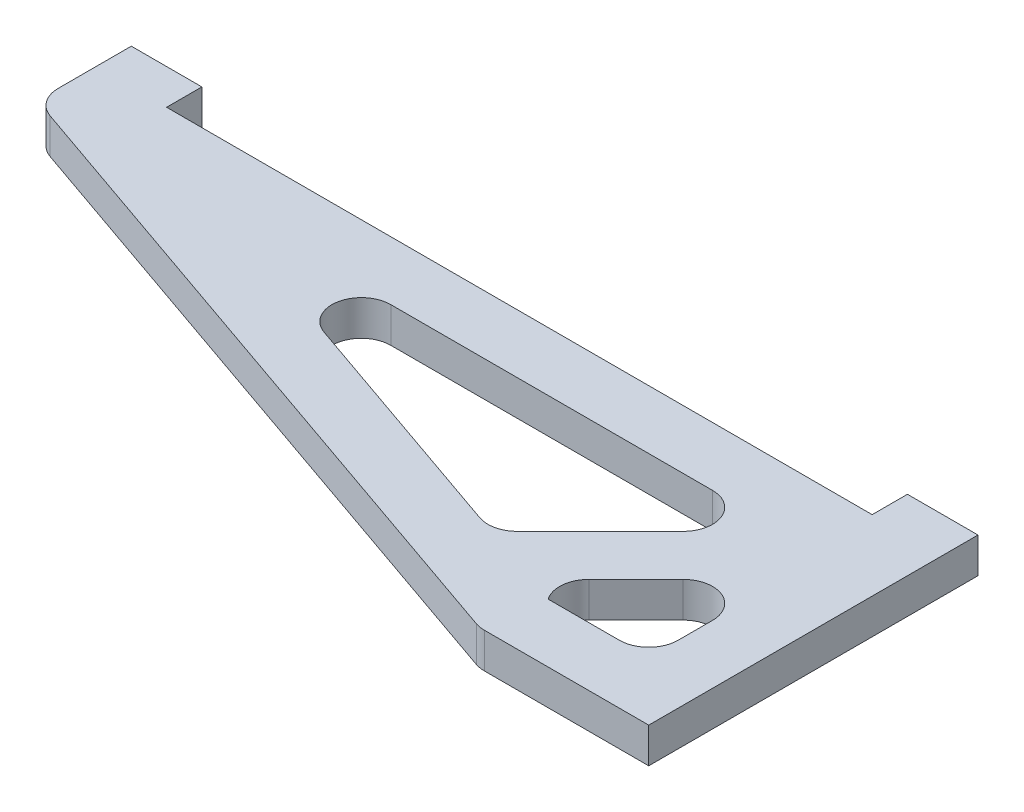
SolidWorks part; units mm, degrees
ref_plane "Front Plane" through (0, 0, 0) normal (0, 0, 1) x (1, 0, 0)
ref_plane "Top Plane" through (0, 0, 0) normal (0, 1, 0) x (1, 0, 0)
ref_plane "Right Plane" through (0, 0, 0) normal (1, 0, 0) x (0, 0, -1)
sketch "Sketch1" plane through (0, 0, 0) normal (0, 1, 0) x (1, 0, 0)
  line L0 (-36, 7.5) -> (21.6, -12.5)
  line L1 (-36, 12.5) -> (36, 12.5)
  line L2 (-36, 12.5) -> (-36, -12.5)
  line L3 (-36, -12.5) -> (36, -12.5)
  line L4 (36, 12.5) -> (36, -12.5)
  line L5 (-36, 12.5) -> (36, -12.5) construction
  line L6 (-36, -12.5) -> (36, 12.5) construction
  line L7 (0, 12.5) -> (0, -12.5) construction
  line L8 (-36, 12.5) -> (-30, 12.5)
  line L9 (-36, 12.5) -> (-36, 15.5)
  line L10 (-36, 15.5) -> (-30, 15.5)
  line L11 (-30, 12.5) -> (-30, 15.5)
  line L12 (36, 12.5) -> (36, 15.5)
  line L13 (36, 15.5) -> (30, 15.5)
  line L14 (30, 12.5) -> (30, 15.5)
  line L15 (36, 12.5) -> (30, 12.5)
  point P0 (0, 0)
  dimension "D1" = 72
  dimension "D2" = 25
  dimension "D3" = 5
  dimension "D4" = 3
  dimension "D5" = 6
extrude "Boss-Extrude1" add sketch "Sketch1" along normal blind 3 contours L4 L1 L2 L0 L3 | L1 L11 L10 L9 | L14 L1 L12 L13 region at (7.9059, 0, -2.7451) region at (-33, 0, -14) region at (33, 0, -14)
sketch "Sketch2" plane through (0, 3, 0) normal (0, 1, 0) x (1, 0, 0)
  line L5 (31, 7.5) -> (17.6607, -5.8393) construction
  line L6 (15.0363, -4.9281) -> (27.4645, 7.5)
  line L7 (31, 3.9645) -> (20.285, -6.7506)
  line L8 (25.6425, -1.393) -> (22.107, 2.1425) construction
  line L9 (31, 7.5) -> (36, 7.5) construction
  line L10 (31, -7.5) -> (31, 7.5)
  line L11 (31, 7.5) -> (-20.7566, 7.5)
  line L12 (-20.7566, 7.5) -> (22.4434, -7.5)
  line L13 (22.4434, -7.5) -> (31, -7.5)
  line L14 (31, -7.5) -> (31, 7.5)
  line L15 (31, 7.5) -> (-20.7566, 7.5)
  line L16 (-20.7566, 7.5) -> (22.4434, -7.5)
  line L17 (22.4434, -7.5) -> (31, -7.5)
  line L18 (36, 15.5) -> (36, -12.5) construction
  dimension "D2" = 45
  dimension "D1" = 5
extrude "Cut-Extrude1" cut sketch "Sketch2" against normal up to next contours L15 L16 L6 | L16 L17 L14 L7 region at (7.2481, 3, -3.3573) region at (27.2868, 3, 3.6183)
fillet "Fillet1" radius 2.5 8 edges at (-36, 1.5, -7.5) (21.6, 1.5, 12.5) (20.285, 1.5, 6.7506) (31, 1.5, -3.9645) (31, 1.5, 7.5) (15.0363, 1.5, 4.9281) (27.4645, 1.5, -7.5) (-20.7566, 1.5, -7.5)
